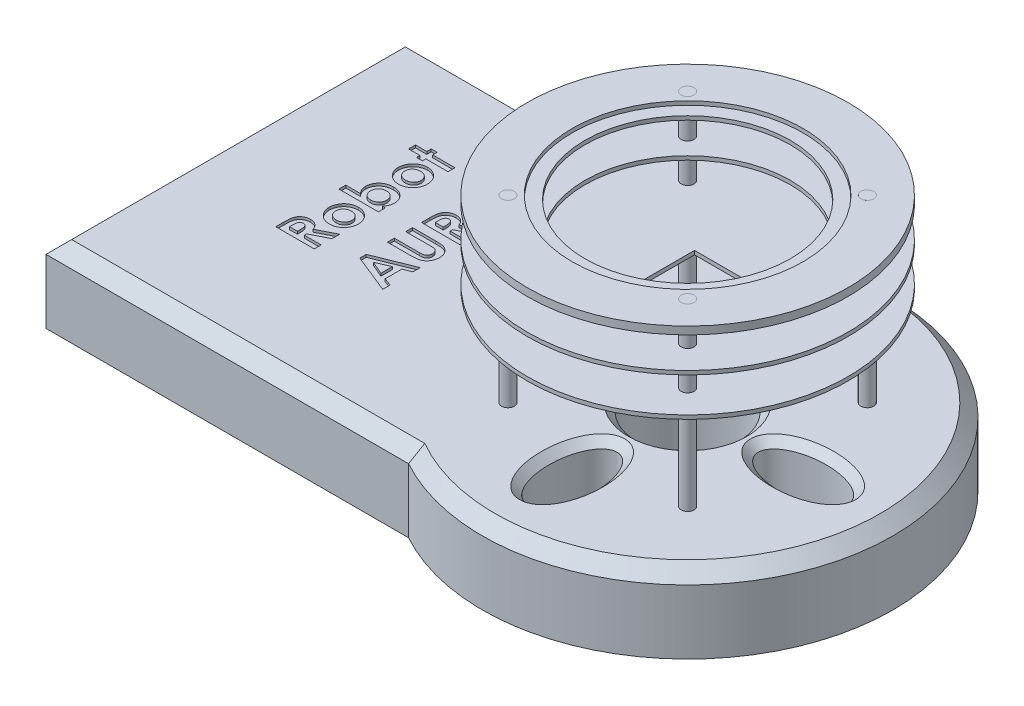
SolidWorks part; units mm, degrees
ref_plane "Front Plane" through (0, 0, 0) normal (0, 0, 1) x (1, 0, 0)
ref_plane "Top Plane" through (0, 0, 0) normal (0, 1, 0) x (1, 0, 0)
ref_plane "Right Plane" through (0, 0, 0) normal (1, 0, 0) x (0, 0, -1)
sketch "Sketch1" plane through (0, 0, 0) normal (0, 1, 0) x (1, 0, 0)
  line L1 (-38.7298, 70) -> (-180, 70)
  line L2 (-38.7298, -70) -> (-180, -70)
  line L3 (-180, 70) -> (-180, -70)
  line L5 (35, 35) -> (-35, 35) construction
  line L6 (35, 35) -> (35, -35) construction
  line L7 (35, -35) -> (-35, -35) construction
  line L8 (-35, 35) -> (-35, -35) construction
  line L9 (35, 35) -> (-35, -35) construction
  line L10 (35, -35) -> (-35, 35) construction
  arc A0 (-38.7298, -70) -> (-38.7298, 70) centre (0, 0) ccw
  circle A1 centre (0, 0) radius 20
  circle A2 centre (-35, -35) radius 2.5
  circle A3 centre (-35, 35) radius 2.5
  circle A4 centre (35, 35) radius 2.5
  circle A5 centre (35, -35) radius 2.5
  ellipse E0 centre (0, -45) end of major axis (0, -62.5) minor radius 9
  ellipse E1 centre (-45, 0) end of major axis (-27.5, 0) minor radius 9
  ellipse E2 centre (0, 45) end of major axis (0, 62.5) minor radius 9
  ellipse E3 centre (45, 0) end of major axis (62.5, 0) minor radius 9
  point P33 (0, 0)
  point P43 (0, 0)
  dimension "D1" = 160
  dimension "D8" = 5
  dimension "D2" = 140
  dimension "D3" = 180
  dimension "D4" = 141.2702
  dimension "D5" = 18
  dimension "D6" = 35
  dimension "D7" = 45
  dimension "D10" = 70
  dimension "D9" = 4
extrude "Boss-Extrude1" add sketch "Sketch1" along normal blind 30
extrude "Boss-Extrude2" add sketch "Sketch1<2>" along normal blind 100 separate body contours A2 | A5 | A4 | A3
sketch "Sketch1<2>" plane through (0, 0, 0) normal (0, 1, 0) x (1, 0, 0) same geometry as "Sketch1"
ref_plane "Plane1" through (0, 100, 0) normal (0, 1, 0) x (1, 0, 0)
sketch "Sketch2" plane through (0, 100, 0) normal (0, 1, 0) x (1, 0, 0)
  circle A0 centre (0, 0) radius 62.5
  circle A1 centre (0, 0) radius 40
  circle A2 centre (0, 0) radius 45
  circle A3 centre (-35, -35) radius 2.5
  circle A4 centre (-35, 35) radius 2.5
  circle A5 centre (35, 35) radius 2.5
  circle A6 centre (35, -35) radius 2.5
  point P17 (0, 0)
  dimension "D1" = 125
  dimension "D2" = 80
  dimension "D3" = 90
  dimension "D4" = 4
extrude "Boss-Extrude3" add sketch "Sketch2" against normal blind 3 separate body contours A0 A6 A5 A4 A3 A2 | A2 A1 region at (-60.7322, 100, 0) region at (-43.7272, 100, 0)
extrude "Cut-Extrude1" cut sketch "Sketch2<3>" against normal blind 1.5 contours A2 A1 | A1 | A1 region at (0, 100, 0) region at (-43.7272, 100, 0)
sketch "Sketch2<3>" plane through (0, 100, 0) normal (0, 1, 0) x (1, 0, 0) same geometry as "Sketch2"
ref_plane "Plane2" through (0, 85, 0) normal (0, 1, 0) x (1, 0, 0)
ref_plane "Plane3" through (0, 70, 0) normal (0, 1, 0) x (1, 0, 0)
sketch "Sketch9" plane through (0, 85, 0) normal (0, 1, 0) x (1, 0, 0)
  circle A0 centre (0, 0) radius 62.5
  circle A1 centre (-35, -35) radius 2.5
  circle A2 centre (-35, 35) radius 2.5
  circle A3 centre (35, 35) radius 2.5
  circle A4 centre (35, -35) radius 2.5
  circle A5 centre (0, 0) radius 40
  point P15 (0, 0)
  dimension "D1" = 4
sketch "Sketch10" plane through (0, 70, 0) normal (0, 1, 0) x (1, 0, 0)
  line L0 (-10, 12.6731) -> (10, 12.6731)
  line L1 (-10, 12.6731) -> (-10, -27.3269)
  line L2 (10, 12.6731) -> (10, -27.3269)
  line L3 (-10, -27.3269) -> (10, -27.3269)
  circle A0 centre (0, 0) radius 62.5
  circle A1 centre (-35, -35) radius 2.5
  circle A2 centre (-35, 35) radius 2.5
  circle A3 centre (35, 35) radius 2.5
  circle A4 centre (35, -35) radius 2.5
  point P6 (0, 12.6731)
  point P15 (0, 0)
  dimension "D2" = 40
  dimension "D3" = 20
  dimension "D1" = 4
extrude "Boss-Extrude4" add sketch "Sketch9" against normal blind 1.5 separate body
extrude "Boss-Extrude5" add sketch "Sketch10" against normal blind 1.5 separate body
chamfer "Chamfer1" distance 5 angle 45 4 edges at (-180, 30, 0) (-109.3649, 30, -70) (80, 30, 0) (-109.3649, 30, 70)
sketch "Sketch11" plane through (0, 30, 0) normal (0, 1, 0) x (1, 0, 0)
  line L0 (-124.5768, -30.0192) -> (-124.5768, 43.2115) construction
  text T0 "Robot\r\nAURA" font "Century Gothic" height 15
  point P3 (-101.423, -35.9423)
  point P4 (-78.8077, 15.75)
  point P5 (-119.7307, -19.7884)
  point P6 (-116.2307, 43.2115)
  point P7 (-116.2307, -30.0192)
extrude "Cut-Extrude2" cut sketch "Sketch11" against normal blind 1
chamfer "Chamfer2" distance 3 angle 45 5 edges at (0, 30, -62.5) (-62.5, 30, 0) (0, 30, 20) (62.5, 30, 0) (0, 30, 62.5)
